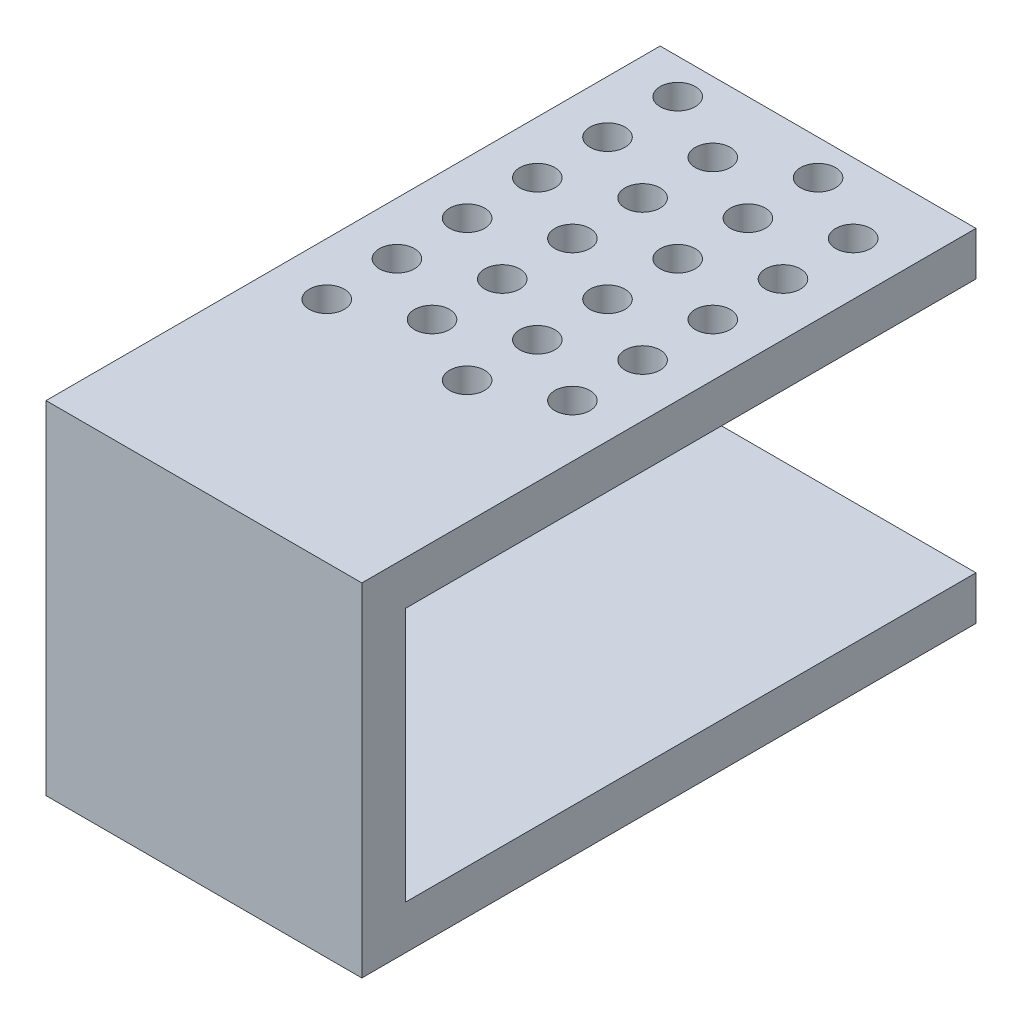
SolidWorks part; units mm, degrees
ref_plane "Front Plane" through (0, 0, 0) normal (0, 0, 1) x (1, 0, 0)
ref_plane "Top Plane" through (0, 0, 0) normal (0, 1, 0) x (1, 0, 0)
ref_plane "Right Plane" through (0, 0, 0) normal (1, 0, 0) x (0, 0, -1)
sketch "Sketch2" plane through (0, 0, 0) normal (0, 1, 0) x (1, 0, 0)
  line L1 (-20, 16) -> (-2, 16)
  line L2 (-20, 16) -> (-20, -8)
  line L3 (-20, -8) -> (-2, -8)
  line L4 (-2, 16) -> (-2, -8)
  circle A0 centre (-17, -6) radius 1
  circle A1 centre (-17, -2) radius 1
  circle A2 centre (-17, 2) radius 1
  circle A3 centre (-17, 6) radius 1
  circle A4 centre (-17, 10) radius 1
  circle A5 centre (-17, 14) radius 1
  circle A6 centre (-13, -4) radius 1
  circle A7 centre (-13, 0) radius 1
  circle A8 centre (-13, 4) radius 1
  circle A9 centre (-13, 8) radius 1
  circle A10 centre (-13, 12) radius 1
  circle A11 centre (-9, -6) radius 1
  circle A12 centre (-9, -2) radius 1
  circle A13 centre (-9, 2) radius 1
  circle A14 centre (-9, 6) radius 1
  circle A15 centre (-9, 10) radius 1
  circle A16 centre (-9, 14) radius 1
  circle A17 centre (-5, -4) radius 1
  circle A18 centre (-5, 0) radius 1
  circle A19 centre (-5, 4) radius 1
  circle A20 centre (-5, 8) radius 1
  circle A21 centre (-5, 12) radius 1
  dimension "D1" = 24
  dimension "D2" = 18
extrude "Boss-Extrude2" add sketch "Sketch2" along normal blind 2.5
sketch "Sketch3" plane through (0, 0, 8) normal (0, 0, 1) x (1, 0, 0)
  line L1 (-20, 2.5) -> (-2, 2.5)
  line L2 (-20, 2.5) -> (-20, 0)
  line L3 (-20, 0) -> (-2, 0)
  line L4 (-2, 2.5) -> (-2, 0)
extrude "Boss-Extrude3" add sketch "Sketch3" along normal blind 11
sketch "Sketch4" plane through (0, 0, 0) normal (0, -1, 0) x (-1, 0, 0)
  line L0 (20, 16) -> (20, -19) construction
  line L1 (2, -19) -> (20, -19)
  line L2 (2, -19) -> (2, -16.5)
  line L3 (2, -16.5) -> (20, -16.5)
  line L4 (20, -19) -> (20, -16.5)
  dimension "D1" = 2.5
extrude "Boss-Extrude4" add sketch "Sketch4" along normal blind 17
sketch "Sketch5" plane through (0, 0, 16.5) normal (0, 0, -1) x (-1, 0, 0)
  line L0 (20, -17) -> (20, 0) construction
  line L1 (2, -17) -> (20, -17)
  line L2 (2, -17) -> (2, -14.5)
  line L3 (2, -14.5) -> (20, -14.5)
  line L4 (20, -17) -> (20, -14.5)
  dimension "D1" = 2.5
extrude "Boss-Extrude5" add sketch "Sketch5" along normal blind 32.5
